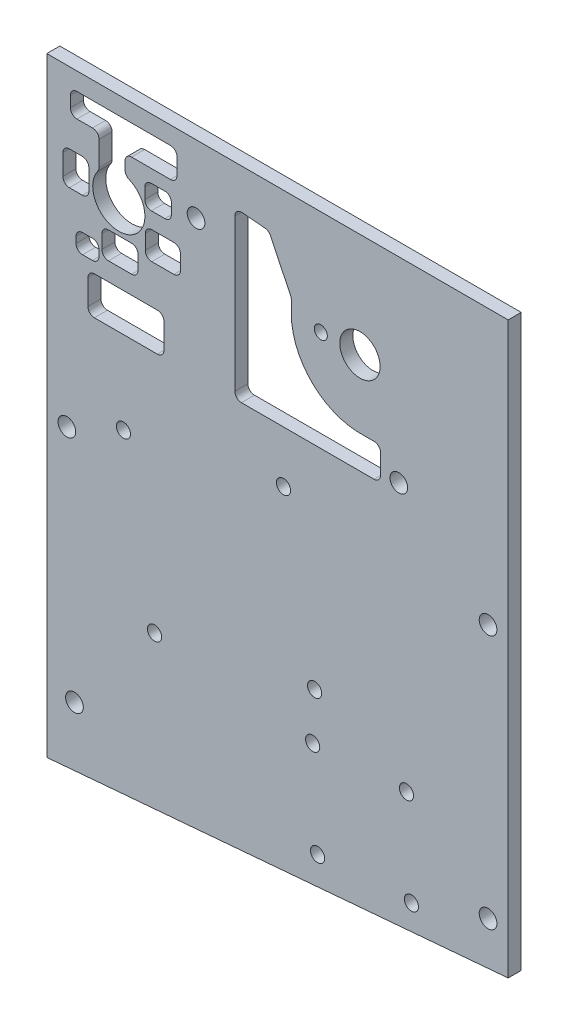
SolidWorks part; units mm, degrees
material "Acrylic (Medium-high impact)"
ref_plane "Front Plane" through (0, 0, 0) normal (0, 0, 1) x (1, 0, 0)
ref_plane "Top Plane" through (0, 0, 0) normal (0, 1, 0) x (1, 0, 0)
ref_plane "Right Plane" through (0, 0, 0) normal (1, 0, 0) x (0, 0, -1)
sketch "Sketch1" plane through (0, 0, 0) normal (0, 0, 1) x (1, 0, 0)
  line L4 (112.268, 0) -> (0, 0)
  line L5 (0, 0) -> (0, -148.336)
  line L6 (0, -148.336) -> (112.268, -138.684)
  line L7 (112.268, -138.684) -> (112.268, 0)
  line L8 (112.268, 0) -> (0, 0)
  line L9 (0, 0) -> (0, -148.336)
  line L10 (0, -148.336) -> (112.268, -138.684)
  line L11 (112.268, -138.684) -> (112.268, 0)
  dimension "D1" = 0
extrude "Boss-Extrude1" add sketch "Sketch1" against normal blind 3.175
hole_wizard "#6 Clearance Hole1" positions "Sketch3" profile "Sketch2" hole size "#6" standard "ANSI Inch" end condition through all
sketch "Sketch3" plane through (0, 0, 0) normal (0, 0, 1) x (1, 0, 0)
  point P0 (6.731, -133.35)
  point P3 (107.3785, -128.5875)
  point P6 (107.3785, -66.675)
  point P9 (4.8895, -76.2)
sketch "Sketch2" plane through (6.731, -133.35, 0) normal (1, 0, 0) x (0, -1, 0)
  line L0 (0, 0) -> (0, 3.175)
  line L1 (0, 3.175) -> (2.1526, 3.175)
  line L2 (2.1526, 3.175) -> (2.1526, 0)
  line L5 (2.1526, 0) -> (0, 0)
  line L11 (0, -6.35) -> (0, 107.95) construction
  dimension "Thru Hole Dia." = 4.3053
  dimension "Thru Hole Depth" = 3.175
hole_wizard "#4 Clearance Hole1" positions "Sketch5" profile "Sketch4" hole size "#4" standard "ANSI Inch" end condition through all
sketch "Sketch5" plane through (0, 0, 0) normal (0, 0, 1) x (1, 0, 0)
  point P0 (18.6445, -70.0322)
  point P3 (57.6028, -62.4595)
  point P6 (65.1755, -101.4178)
  point P9 (26.2172, -108.9905)
  point P12 (65.8919, -135.8375)
  point P15 (88.7205, -134.6411)
  point P18 (87.5241, -111.8125)
  point P21 (64.6955, -113.0089)
sketch "Sketch4" plane through (18.6445, -70.0322, 0) normal (1, 0, 0) x (0, -1, 0)
  line L0 (0, 0) -> (0, 3.175)
  line L1 (0, 3.175) -> (1.7272, 3.175)
  line L2 (1.7272, 3.175) -> (1.7272, 0)
  line L5 (1.7272, 0) -> (0, 0)
  line L11 (0, -6.35) -> (0, 107.95) construction
  dimension "Thru Hole Dia." = 3.4544
  dimension "Thru Hole Depth" = 3.175
hole_wizard "#6 Clearance Hole2" positions "Sketch7" profile "Sketch6" hole size "#6" standard "ANSI Inch" end condition through all
sketch "Sketch7" plane through (0, 0, 0) normal (0, 0, 1) x (1, 0, 0)
  point P0 (36.322, -16.51)
  point P3 (85.6615, -47.625)
sketch "Sketch6" plane through (36.322, -16.51, 0) normal (1, 0, 0) x (0, -1, 0)
  line L0 (0, 0) -> (0, 3.175)
  line L1 (0, 3.175) -> (2.1526, 3.175)
  line L2 (2.1526, 3.175) -> (2.1526, 0)
  line L5 (2.1526, 0) -> (0, 0)
  line L11 (0, -6.35) -> (0, 107.95) construction
  dimension "Thru Hole Dia." = 4.3053
  dimension "Thru Hole Depth" = 3.175
hole_wizard "3/8 (0.386) Diameter Hole1" positions "Sketch11" profile "Sketch10" hole size "3/8" standard "ANSI Inch" end condition through all
sketch "Sketch11" plane through (0, 0, 0) normal (0, 0, 1) x (1, 0, 0)
  point P0 (76.2, -25.4)
sketch "Sketch10" plane through (76.2, -25.4, 0) normal (1, 0, 0) x (0, -1, 0)
  line L0 (0, 0) -> (0, 3.175)
  line L1 (0, 3.175) -> (4.9022, 3.175)
  line L2 (4.9022, 3.175) -> (4.9022, 0)
  line L5 (4.9022, 0) -> (0, 0)
  line L11 (0, -6.35) -> (0, 107.95) construction
  dimension "Thru Hole Dia." = 9.8044
  dimension "Thru Hole Depth" = 3.175
hole_wizard "1/8 (0.125) Diameter Hole1" positions "Sketch16" profile "Sketch17" hole size "1/8" standard "ANSI Inch" end condition through all
sketch "Sketch16" plane through (0, 0, 0) normal (0, 0, 1) x (1, 0, 0)
  line L0 (66.675, -25.4) -> (76.2, -25.4) construction
  line L1 (76.2, -25.4) -> (76.2, 0) construction
  line L2 (112.268, 0) -> (0, 0) construction
  point P0 (66.675, -25.4)
  dimension "D1" = 9.525
  dimension "D2" = 90
sketch "Sketch17" plane through (66.675, -25.4, 0) normal (1, 0, 0) x (0, -1, 0)
  line L0 (0, 0) -> (0, 3.175)
  line L1 (0, 3.175) -> (1.5875, 3.175)
  line L2 (1.5875, 3.175) -> (1.5875, 0)
  line L5 (1.5875, 0) -> (0, 0)
  line L11 (0, -6.35) -> (0, 107.95) construction
  dimension "Thru Hole Dia." = 3.175
  dimension "Thru Hole Depth" = 3.175
hole_wizard "1/2 (0.5) Diameter Hole1" positions "Sketch13" profile "Sketch12" hole size "1/2" standard "ANSI Inch" end condition through all
sketch "Sketch13" plane through (0, 0, 0) normal (0, 0, 1) x (1, 0, 0)
  point P0 (17.526, -22.352)
sketch "Sketch12" plane through (17.526, -22.352, 0) normal (1, 0, 0) x (0, -1, 0)
  line L0 (0, 0) -> (0, 3.175)
  line L1 (0, 3.175) -> (6.35, 3.175)
  line L2 (6.35, 3.175) -> (6.35, 0)
  line L5 (6.35, 0) -> (0, 0)
  line L11 (0, -6.35) -> (0, 107.95) construction
  dimension "Thru Hole Dia." = 12.7
  dimension "Thru Hole Depth" = 3.175
sketch "Sketch15" plane through (0, 0, 0) normal (0, 0, 1) x (1, 0, 0)
  line L0 (7.3391, -4.3284) -> (30.0964, -4.3284)
  line L1 (31.6839, -5.9159) -> (31.6839, -9.9082)
  line L2 (30.0964, -11.4957) -> (20.631, -11.4957)
  line L3 (19.0435, -13.0832) -> (19.0435, -18.5245)
  line L4 (17.456, -20.112) -> (14.3108, -20.112)
  line L5 (12.7233, -18.5245) -> (12.7233, -11.7148)
  line L6 (11.1358, -10.1273) -> (7.3391, -10.1273)
  line L7 (5.7516, -8.5398) -> (5.7516, -5.9159)
  line L8 (45.7668, -11.3344) -> (45.7668, -48.3053)
  line L20 (59.3363, -21.3703) -> (54.4079, -11.1365)
  line L21 (53.1157, -10.2438) -> (47.4924, -9.7529)
  line L22 (25.4335, -14.6362) -> (28.7265, -14.6362)
  line L23 (30.314, -16.2237) -> (30.314, -18.8368)
  line L24 (28.7265, -20.4243) -> (25.4335, -20.4243)
  line L25 (23.846, -18.8368) -> (23.846, -16.2237)
  line L26 (25.5483, -24.3452) -> (30.932, -24.3452)
  line L27 (32.5195, -25.9327) -> (32.5195, -29.489)
  line L28 (30.932, -31.0765) -> (25.5483, -31.0765)
  line L29 (23.9608, -29.489) -> (23.9608, -25.9327)
  line L30 (14.9979, -29.6607) -> (20.6331, -29.6607)
  line L31 (22.2206, -31.2482) -> (22.2206, -34.595)
  line L32 (20.6331, -36.1825) -> (14.9979, -36.1825)
  line L33 (13.4104, -34.595) -> (13.4104, -31.2482)
  line L34 (5.5045, -17.3366) -> (8.6394, -17.3366)
  line L35 (10.2269, -18.9241) -> (10.2269, -23.937)
  line L36 (8.6394, -25.5245) -> (5.5045, -25.5245)
  line L37 (3.917, -23.937) -> (3.917, -18.9241)
  line L38 (8.6994, -33.3754) -> (11.1093, -33.3754)
  line L39 (12.6968, -34.9629) -> (12.6968, -36.4594)
  line L40 (11.1093, -38.0469) -> (8.6994, -38.0469)
  line L41 (7.1119, -36.4594) -> (7.1119, -34.9629)
  line L42 (11.5858, -40.6238) -> (26.9166, -40.6238)
  line L43 (28.5041, -42.2113) -> (28.5041, -48.3053)
  line L44 (26.9166, -49.8928) -> (11.5858, -49.8928)
  line L45 (9.9983, -48.3053) -> (9.9983, -42.2113)
  line L46 (81.2243, -43.4934) -> (81.2243, -48.3053)
  line L47 (75.5632, -41.9059) -> (79.6368, -41.9059)
  line L48 (59.4935, -22.0591) -> (59.4935, -25.0385)
  line L49 (79.6368, -49.8928) -> (47.3543, -49.8928)
  arc A11 (45.7668, -11.3344) -> (47.4924, -9.7529) centre (47.3543, -11.3344) cw
  arc A12 (54.4079, -11.1365) -> (53.1157, -10.2438) centre (52.9777, -11.8253) ccw
  arc A13 (28.7265, -14.6362) -> (30.314, -16.2237) centre (28.7265, -16.2237) cw
  arc A14 (30.314, -18.8368) -> (28.7265, -20.4243) centre (28.7265, -18.8368) cw
  arc A15 (25.4335, -20.4243) -> (23.846, -18.8368) centre (25.4335, -18.8368) cw
  arc A16 (25.4335, -14.6362) -> (23.846, -16.2237) centre (25.4335, -16.2237) ccw
  arc A17 (30.932, -24.3452) -> (32.5195, -25.9327) centre (30.932, -25.9327) cw
  arc A18 (32.5195, -29.489) -> (30.932, -31.0765) centre (30.932, -29.489) cw
  arc A19 (25.5483, -31.0765) -> (23.9608, -29.489) centre (25.5483, -29.489) cw
  arc A20 (25.5483, -24.3452) -> (23.9608, -25.9327) centre (25.5483, -25.9327) ccw
  arc A21 (20.6331, -29.6607) -> (22.2206, -31.2482) centre (20.6331, -31.2482) cw
  arc A22 (22.2206, -34.595) -> (20.6331, -36.1825) centre (20.6331, -34.595) cw
  arc A23 (14.9979, -36.1825) -> (13.4104, -34.595) centre (14.9979, -34.595) cw
  arc A24 (14.9979, -29.6607) -> (13.4104, -31.2482) centre (14.9979, -31.2482) ccw
  arc A25 (8.6394, -17.3366) -> (10.2269, -18.9241) centre (8.6394, -18.9241) cw
  arc A26 (10.2269, -23.937) -> (8.6394, -25.5245) centre (8.6394, -23.937) cw
  arc A27 (5.5045, -25.5245) -> (3.917, -23.937) centre (5.5045, -23.937) cw
  arc A28 (5.5045, -17.3366) -> (3.917, -18.9241) centre (5.5045, -18.9241) ccw
  arc A29 (11.1093, -33.3754) -> (12.6968, -34.9629) centre (11.1093, -34.9629) cw
  arc A30 (12.6968, -36.4594) -> (11.1093, -38.0469) centre (11.1093, -36.4594) cw
  arc A31 (8.6994, -38.0469) -> (7.1119, -36.4594) centre (8.6994, -36.4594) cw
  arc A32 (8.6994, -33.3754) -> (7.1119, -34.9629) centre (8.6994, -34.9629) ccw
  arc A33 (26.9166, -40.6238) -> (28.5041, -42.2113) centre (26.9166, -42.2113) cw
  arc A34 (28.5041, -48.3053) -> (26.9166, -49.8928) centre (26.9166, -48.3053) cw
  arc A35 (11.5858, -49.8928) -> (9.9983, -48.3053) centre (11.5858, -48.3053) cw
  arc A36 (11.5858, -40.6238) -> (9.9983, -42.2113) centre (11.5858, -42.2113) ccw
  arc A37 (30.0964, -4.3284) -> (31.6839, -5.9159) centre (30.0964, -5.9159) cw
  arc A38 (7.3391, -4.3284) -> (5.7516, -5.9159) centre (7.3391, -5.9159) ccw
  arc A39 (7.3391, -10.1273) -> (5.7516, -8.5398) centre (7.3391, -8.5398) cw
  arc A40 (31.6839, -9.9082) -> (30.0964, -11.4957) centre (30.0964, -9.9082) cw
  arc A41 (12.7233, -11.7148) -> (11.1358, -10.1273) centre (11.1358, -11.7148) ccw
  arc A42 (20.631, -11.4957) -> (19.0435, -13.0832) centre (20.631, -13.0832) ccw
  arc A43 (19.0435, -18.5245) -> (17.456, -20.112) centre (17.456, -18.5245) cw
  arc A44 (14.3108, -20.112) -> (12.7233, -18.5245) centre (14.3108, -18.5245) cw
  arc A45 (59.4935, -25.0385) -> (75.5632, -41.9059) centre (76.3806, -25.0385) ccw
  arc A46 (47.3543, -49.8928) -> (45.7668, -48.3053) centre (47.3543, -48.3053) cw
  arc A47 (81.2243, -48.3053) -> (79.6368, -49.8928) centre (79.6368, -48.3053) cw
  arc A48 (81.2243, -43.4934) -> (79.6368, -41.9059) centre (79.6368, -43.4934) ccw
  arc A49 (59.3363, -21.3703) -> (59.4935, -22.0591) centre (57.906, -22.0591) cw
  dimension "D1" = 1.5875
  dimension "D2" = 1.5875
  dimension "D3" = 1.5875
  dimension "D4" = 1.5875
  dimension "D5" = 1.5875
  dimension "D6" = 1.5875
extrude "Backlighting LED Holes" cut sketch "Sketch15" against normal through all
fillet "Thin Section Fillet" radius 1.5875 2 edges at (19.0435, -16.186, -1.5875) (12.7233, -18.1979, -1.5875)
